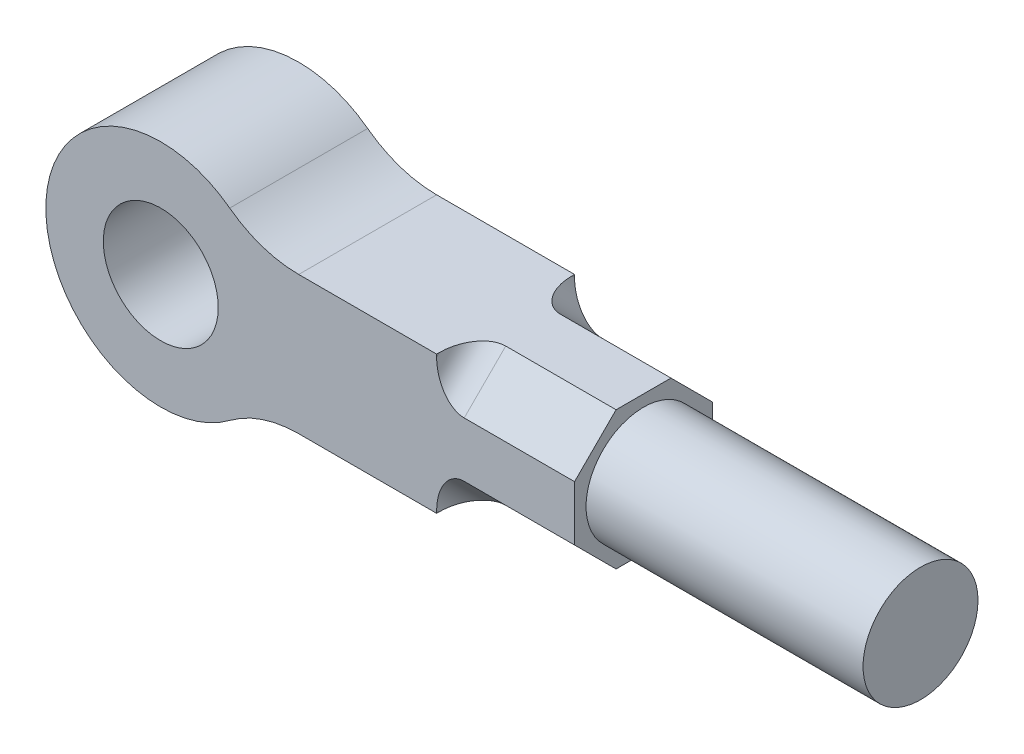
SolidWorks part; units mm, degrees
ref_plane "Front Plane" through (0, 0, 0) normal (0, 0, 1) x (1, 0, 0)
ref_plane "Top Plane" through (0, 0, 0) normal (0, 1, 0) x (1, 0, 0)
ref_plane "Right Plane" through (0, 0, 0) normal (1, 0, 0) x (0, 0, -1)
sketch "Sketch1" plane through (0, 0, 0) normal (0, 0, 1) x (1, 0, 0)
  line L0 (0, 0) -> (100.3483, 0) construction
  line L2 (60, 30) -> (180, 30)
  line L4 (60, -30) -> (180, -30)
  line L5 (180, 30) -> (180, -30)
  circle A0 centre (0, 0) radius 25
  arc A1 (30, 40) -> (30, -40) centre (0, 0) ccw
  arc A2 (30, -40) -> (60, -30) centre (60, -80) cw
  arc A3 (60, 30) -> (30, 40) centre (60, 80) cw
  point P12 (40, 30)
  dimension "D1" = 100
  dimension "D2" = 50
  dimension "D5" = 50
  dimension "D3" = 60
  dimension "D4" = 140
extrude "Boss-Extrude1" add sketch "Sketch1" along normal blind 60
sketch "Sketch2" plane through (180, 0, 0) normal (1, 0, 0) x (0, 0, -1)
  line L0 (0, 11.94) -> (0, 30)
  line L1 (0, -30) -> (0, 30) construction
  line L2 (0, 30) -> (-18.06, 30)
  line L3 (-60, 30) -> (0, 30) construction
  line L4 (-18.06, 30) -> (0, 11.94)
  line L5 (0, -11.94) -> (-18.06, -30)
  line L6 (-18.06, -30) -> (0, -30)
  line L7 (0, -30) -> (0, -11.94)
  line L8 (-41.94, -30) -> (-60, -11.94)
  line L9 (-60, -11.94) -> (-60, -30)
  line L10 (-60, -30) -> (-41.94, -30)
  line L11 (-60, 11.94) -> (-41.94, 30)
  line L12 (-41.94, 30) -> (-60, 30)
  line L13 (-60, 30) -> (-60, 11.94)
  circle A0 centre (-30, 0) radius 25
  point P23 (-30, 0)
  line M5 (0, -30) -> (0, 30)
  line M6 (0, 30) -> (-60, 30)
  line M7 (-60, 30) -> (-60, -30)
  line M8 (-60, -30) -> (0, -30)
  dimension "D1" = 50
  dimension "D2" = 30
  dimension "D3" = 18.06
  dimension "D4" = 18.06
  dimension "D5" = 4
extrude "Cut-Extrude1" cut sketch "Sketch2" against normal blind 60 contours L11 M7 M6 | L5 M5 M8 | L2 L4 L0 | L8 L9 L10 region at (180, -23.98, 6.02) region at (180, 23.98, 53.98)
extrude "Boss-Extrude2" add sketch "Sketch2<3>" along normal blind 120.5 contours A0 region at (180, 0, 30)
sketch "Sketch2<3>" plane through (180, 0, 0) normal (1, 0, 0) x (0, 0, -1) same geometry as "Sketch2"
fillet "Fillet1" radius 12 4 edges at (120, -20.97, 9.03) (120, 20.97, 9.03) (120, -20.97, 50.97) (120, 20.97, 50.97)
